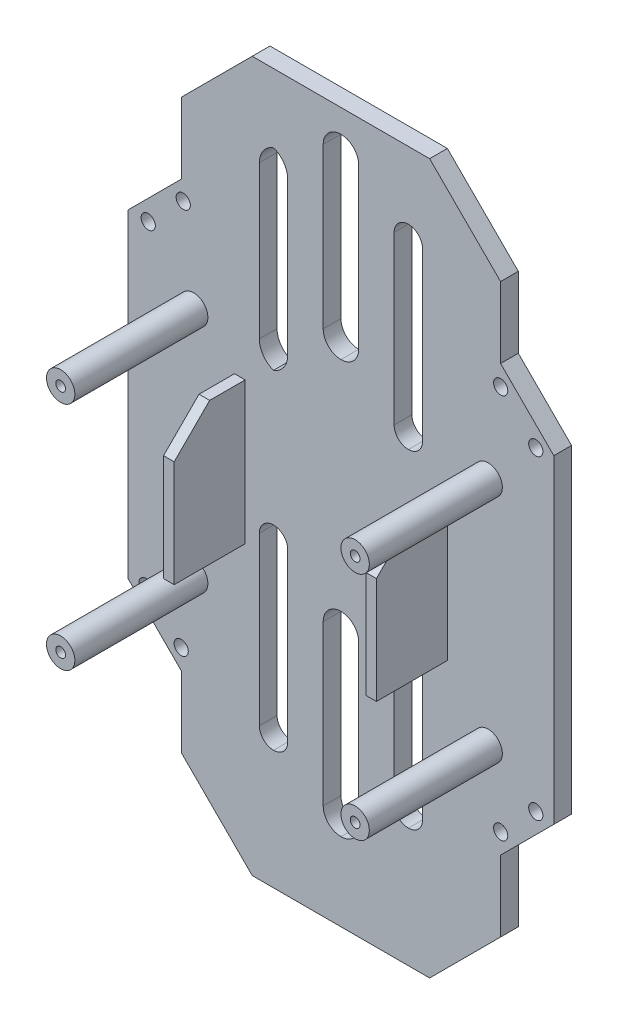
SolidWorks part; units mm, degrees
ref_plane "Plan de face" through (0, 0, 0) normal (0, 0, 1) x (1, 0, 0)
ref_plane "Plan de dessus" through (0, 0, 0) normal (0, 1, 0) x (1, 0, 0)
ref_plane "Plan de droite" through (0, 0, 0) normal (1, 0, 0) x (0, 0, -1)
sketch "Esquisse1" plane through (0, 0, 0) normal (0, 0, 1) x (1, 0, 0)
  line L0 (-41.0719, 30.2056) -> (78.9281, 30.2056)
  line L1 (78.9281, 30.2056) -> (78.9281, -89.7944)
  line L2 (78.9281, -89.7944) -> (-41.0719, -89.7944)
  line L3 (-41.0719, -89.7944) -> (-41.0719, 30.2056)
  dimension "D1" = 120
  dimension "D2" = 120
extrude "Boss.-Extru.2" add sketch "Esquisse1" along normal blind 5
sketch "Esquisse3" plane through (0, 0, 0) normal (0, 0, -1) x (-1, 0, 0)
sketch "Esquisse7" plane through (0, 0, 5) normal (0, 0, 1) x (1, 0, 0)
sketch "Esquisse9" plane through (0, 0, 5) normal (0, 0, 1) x (1, 0, 0)
  line L0 (-41.0719, -89.7944) -> (78.9281, -89.7944) construction
  line L1 (78.9281, -89.7944) -> (78.9281, 30.2056) construction
  circle A0 centre (-22.5719, -64.7944) radius 4
  circle A1 centre (-22.5719, 0.2056) radius 4
  circle A2 centre (60.4281, 0.2056) radius 4
  circle A3 centre (60.4281, -64.7944) radius 4
  dimension "D5" = 8
  dimension "D6" = 8
  dimension "D7" = 8
  dimension "D8" = 8
  dimension "D1" = 83
  dimension "D2" = 83
  dimension "D3" = 18.5
  dimension "D4" = 65
  dimension "D9" = 25
  dimension "D10" = 25
  dimension "D11" = 18.5
extrude "Boss.-Extru.4" add sketch "Esquisse9" along normal blind 37.5
chamfer "Chanfrein5" distance 15 angle 45 1 edges at (78.9281, -89.7944, 2.5)
chamfer "Chanfrein6" distance 15 angle 45 1 edges at (78.9281, 30.2056, 2.5)
chamfer "Chanfrein7" distance 15 angle 45 1 edges at (-41.0719, 30.2056, 2.5)
chamfer "Chanfrein8" distance 15 angle 45 1 edges at (-41.0719, -89.7944, 2.5)
hole_wizard "Dégagement #61" positions "Esquisse3D4" profile "Esquisse18" hole size "#6" standard "Ansi Pouces"
sketch3d "Esquisse3D4"
  line L0 (-22.5719, -64.7944, 42.5) -> (-22.5719, -64.7944, 5) construction
  line L1 (60.4281, -64.7944, 42.5) -> (60.4281, -64.7944, 5) construction
  line L2 (60.4281, 0.2056, 42.5) -> (60.4281, 0.2056, 5) construction
  line L3 (-22.5719, 0.2056, 42.5) -> (-22.5719, 0.2056, 5) construction
  point P0 (-22.5719, -64.7944, 42.5)
  point P4 (60.4281, -64.7944, 42.5)
  point P8 (60.4281, 0.2056, 42.5)
  point P12 (-22.5719, 0.2056, 42.5)
sketch "Esquisse18" plane through (-22.5719, -64.7944, 42.5) normal (1, 0, 0) x (0, -1, 0)
  line L0 (0, 0) -> (0, 15.8262)
  line L1 (0, 15.8262) -> (1.375, 15)
  line L2 (1.375, 15) -> (1.375, 0)
  line L5 (1.375, 0) -> (0, 0)
  line L10 (0, 15.8262) -> (-1.375, 15) construction
  line L11 (0, -6.35) -> (0, 107.95) construction
  dimension "Diamètre du perçage" = 2.75
  dimension "Profondeur du perçage" = 15
  dimension "Angle de pointe" = 118
cosmetic thread "Représentation de filetage1" parameters "D2"=4
sketch "Esquisse21" plane through (0, -89.7944, 0) normal (0, -1, 0) x (-1, 0, 0)
  line L0 (26.0719, -5) -> (26.0719, 0)
  line L1 (26.0719, 0) -> (-63.9281, 0)
  line L2 (-63.9281, 0) -> (-63.9281, -5)
  line L3 (-63.9281, -5) -> (26.0719, -5)
extrude "Boss.-Extru.7" add sketch "Esquisse21" along normal blind 40
sketch "Esquisse22" plane through (0, 30.2056, 0) normal (0, 1, 0) x (1, 0, 0)
  line L0 (63.9281, -5) -> (63.9281, 0)
  line L1 (63.9281, 0) -> (-26.0719, 0) construction
  line L2 (63.9281, 0) -> (-26.0719, 0)
  line L3 (-26.0719, 0) -> (-26.0719, -5)
  line L4 (-26.0719, -5) -> (63.9281, -5)
extrude "Boss.-Extru.8" add sketch "Esquisse22" along normal blind 40
chamfer "Chanfrein23" distance 20 angle 45 4 edges at (-26.0719, -129.7944, 2.5) (63.9281, -129.7944, 2.5) (-26.0719, 70.2056, 2.5) (63.9281, 70.2056, 2.5)
sketch "Esquisse23" plane through (0, 0, 5) normal (0, 0, 1) x (1, 0, 0)
  line L0 (-41.0719, -74.7944) -> (-26.0719, -89.7944) construction
  line L1 (-26.0719, 30.2056) -> (-41.0719, 15.2056) construction
  line L3 (78.9281, 15.2056) -> (63.9281, 30.2056) construction
  line L5 (63.9281, -89.7944) -> (78.9281, -74.7944) construction
  circle A0 centre (-35.9963, -74.2132) radius 2
  circle A1 centre (-26.0968, -84.1127) radius 2
  circle A2 centre (-25.5241, 25.0966) radius 2
  circle A3 centre (-35.3901, 15.1637) radius 2
  circle A4 centre (63.9532, 24.5237) radius 2
  circle A5 centre (73.8527, 14.6242) radius 2
  circle A6 centre (63.9532, -84.1124) radius 2
  circle A7 centre (73.8527, -74.2129) radius 2
  dimension "D3" = 4
  dimension "D4" = 4
  dimension "D6" = 4
  dimension "D7" = 4
  dimension "D10" = 5.6818
  dimension "D15" = 4
  dimension "D16" = 4
  dimension "D19" = 14
  dimension "D23" = 4
  dimension "D24" = 4
  dimension "D1" = 4
  dimension "D2" = 4
  dimension "D5" = 14
  dimension "D8" = 14
  dimension "D9" = 4
  dimension "D11" = 5.682
  dimension "D12" = 5.109
  dimension "D13" = 14
  dimension "D14" = 4
  dimension "D17" = 4
  dimension "D18" = 5.682
  dimension "D20" = 4
  dimension "D21" = 5.682
  dimension "D22" = 4
extrude "Enlèv. mat.-Extru.1" cut sketch "Esquisse23" against normal blind 10
sketch "Esquisse24" plane through (0, 0, 5) normal (0, 0, 1) x (1, 0, 0)
  line L0 (63.9281, -89.7944) -> (78.9281, -74.7944) construction
  circle A0 centre (63.5389, -84.5268) radius 2.5407
  circle A1 centre (73.4383, -74.6273) radius 2.5147
  dimension "D1" = 4
  dimension "D2" = 4
  dimension "D3" = 14
  dimension "D4" = 5.282
sketch "Sketch1" plane through (0, 0, 5) normal (0, 0, 1) x (1, 0, 0)
  line L1 (13.9281, -107.7944) -> (23.9281, -107.7944)
  line L2 (13.9281, -107.7944) -> (13.9281, -52.7944)
  line L3 (13.9281, -52.7944) -> (23.9281, -52.7944)
  line L4 (23.9281, -107.7944) -> (23.9281, -52.7944)
  line L6 (43.9281, -129.7944) -> (-6.0719, -129.7944) construction
  dimension "D1" = 10
  dimension "D2" = 55
  dimension "D3" = 40
  dimension "D4" = 22
extrude "Cut-Extrude2" cut sketch "Sketch1" against normal blind 5 contours L2 L1 L4 L3
fillet "Fillet2" radius 5 1 edges at (13.9281, -107.7944, 2.5)
fillet "Fillet3" radius 5 3 edges at (13.9281, -52.7944, 2.5) (23.9281, -52.7944, 2.5) (23.9281, -107.7944, 2.5)
sketch "Sketch2" plane through (0, 0, 5) normal (0, 0, 1) x (1, 0, 0)
  line L0 (23.9281, -102.7944) -> (23.9281, -57.7944) construction
  line L1 (41.9281, -96.2103) -> (33.9281, -96.2103)
  line L2 (41.9281, -96.2103) -> (41.9281, -41.2103)
  line L3 (41.9281, -41.2103) -> (33.9281, -41.2103)
  line L4 (33.9281, -96.2103) -> (33.9281, -41.2103)
  line L5 (13.9281, -102.7944) -> (13.9281, -57.7944) construction
  line L6 (3.9281, -96.2103) -> (-4.0719, -96.2103)
  line L7 (3.9281, -96.2103) -> (3.9281, -41.2103)
  line L8 (3.9281, -41.2103) -> (-4.0719, -41.2103)
  line L9 (-4.0719, -96.2103) -> (-4.0719, -41.2103)
  dimension "D1" = 10
  dimension "D2" = 10
  dimension "D3" = 8
  dimension "D4" = 8
  dimension "D5" = 55
  dimension "D6" = 55
sketch "Sketch3" plane through (0, 0, 5) normal (0, 0, 1) x (1, 0, 0)
  line L0 (78.9281, -74.7944) -> (78.9281, 15.2056) construction
  line L1 (23.9281, 63.6661) -> (13.9281, 63.6661)
  line L2 (23.9281, 63.6661) -> (23.9281, 8.6661)
  line L3 (23.9281, 8.6661) -> (13.9281, 8.6661)
  line L4 (13.9281, 63.6661) -> (13.9281, 8.6661)
  dimension "D1" = 10
  dimension "D2" = 55
  dimension "D3" = 55
extrude "Cut-Extrude4" cut sketch "Sketch3" against normal blind 5
fillet "Fillet11" radius 5 4 edges at (13.9281, 63.6661, 2.5) (23.9281, 63.6661, 2.5) (23.9281, 8.6661, 2.5) (13.9281, 8.6661, 2.5)
extrude "Cut-Extrude5" cut sketch "Sketch2" against normal blind 8
sketch "Sketch4" plane through (0, 0, 5) normal (0, 0, 1) x (1, 0, 0)
  line L0 (13.9281, 58.6661) -> (13.9281, 13.6661) construction
  line L1 (-4.0719, 51.2056) -> (3.9281, 51.2056)
  line L2 (-4.0719, 51.2056) -> (-4.0719, -3.7944)
  line L3 (-4.0719, -3.7944) -> (3.9281, -3.7944)
  line L4 (3.9281, 51.2056) -> (3.9281, -3.7944)
  line L5 (33.9281, 51.2056) -> (41.9281, 51.2056)
  line L6 (33.9281, 51.2056) -> (33.9281, -3.7944)
  line L7 (33.9281, -3.7944) -> (41.9281, -3.7944)
  line L8 (41.9281, 51.2056) -> (41.9281, -3.7944)
  line L9 (23.9281, 13.6661) -> (23.9281, 58.6661) construction
  line L10 (-6.0719, 70.2056) -> (43.9281, 70.2056) construction
  dimension "D1" = 8
  dimension "D2" = 55
  dimension "D3" = 55
  dimension "D4" = 8
  dimension "D5" = 10
  dimension "D6" = 10
  dimension "D7" = 19
  dimension "D8" = 19
extrude "Cut-Extrude6" cut sketch "Sketch4" against normal blind 8
fillet "Fillet12" radius 4 4 edges at (33.9281, 51.2056, 2.5) (41.9281, 51.2056, 2.5) (41.9281, -3.7944, 2.5) (33.9281, -3.7944, 2.5)
fillet "Fillet13" radius 6 4 edges at (-4.0719, -3.7944, 2.5) (3.9281, -3.7944, 2.5) (-4.0719, 51.2056, 2.5) (3.9281, 51.2056, 2.5)
fillet "Fillet14" radius 4 4 edges at (3.9281, -41.2103, 2.5) (-4.0719, -41.2103, 2.5) (-4.0719, -96.2103, 2.5) (3.9281, -96.2103, 2.5)
fillet "Fillet15" radius 4 4 edges at (41.9281, -96.2103, 2.5) (33.9281, -96.2103, 2.5) (33.9281, -41.2103, 2.5) (41.9281, -41.2103, 2.5)
sketch "Sketch5" plane through (0, 0, 5) normal (0, 0, 1) x (1, 0, 0)
  line L0 (-6.0719, 70.2056) -> (43.9281, 70.2056) construction
  line L1 (-11.0719, -9.7944) -> (-8.0719, -9.7944)
  line L2 (-11.0719, -9.7944) -> (-11.0719, -49.7944)
  line L3 (-11.0719, -49.7944) -> (-8.0719, -49.7944)
  line L4 (-8.0719, -9.7944) -> (-8.0719, -49.7944)
  line L5 (45.9281, -9.7944) -> (48.9281, -9.7944)
  line L6 (45.9281, -9.7944) -> (45.9281, -49.7944)
  line L7 (45.9281, -49.7944) -> (48.9281, -49.7944)
  line L8 (48.9281, -9.7944) -> (48.9281, -49.7944)
  line L9 (-41.0719, 15.2056) -> (-41.0719, -74.7944) construction
  dimension "D1" = 40
  dimension "D2" = 40
  dimension "D3" = 80
  dimension "D4" = 80
  dimension "D5" = 3
  dimension "D6" = 3
  dimension "D7" = 54
  dimension "D8" = 30
extrude "Boss-Extrude1" add sketch "Sketch5" along normal blind 20
chamfer "Chamfer1" distance 10 angle 45 1 edges at (47.4281, -9.7944, 25)
chamfer "Chamfer2" distance 10 angle 45 1 edges at (-9.5719, -9.7944, 25)
